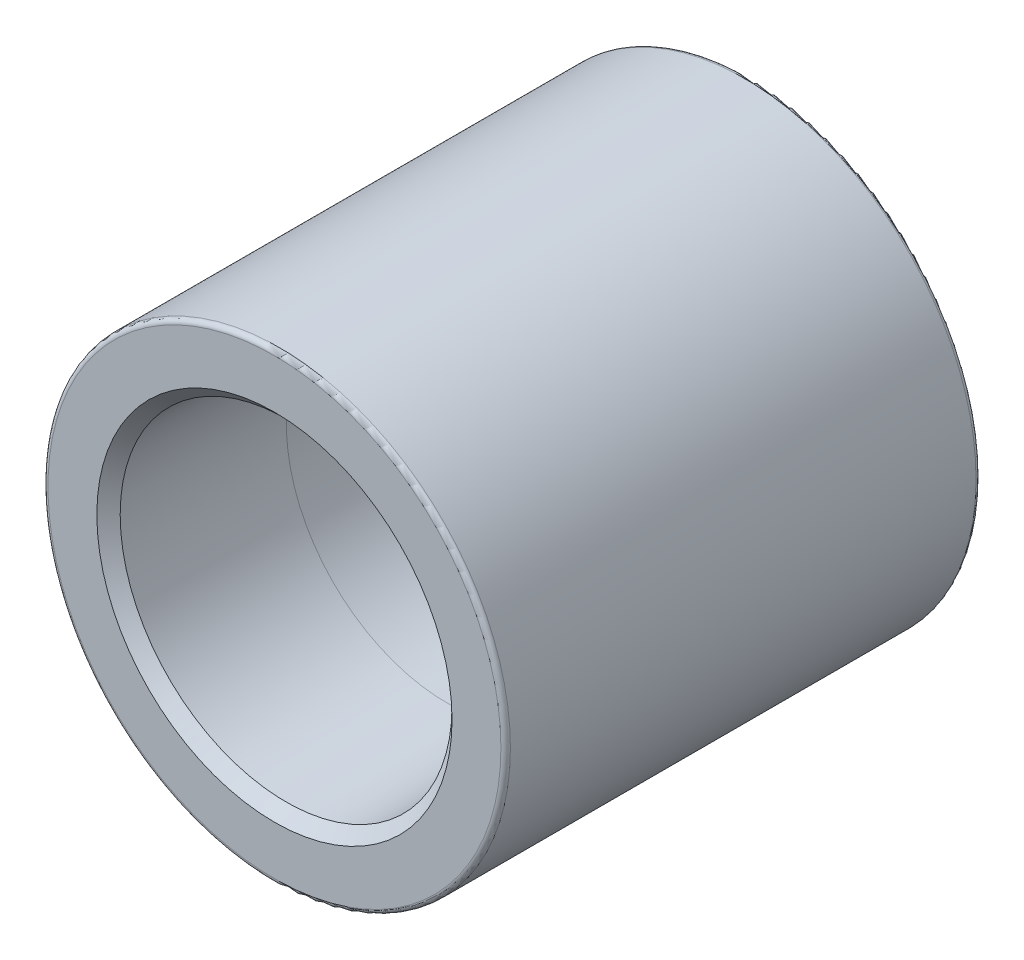
SolidWorks part; units mm, degrees
ref_plane "Front Plane" through (0, 0, 0) normal (0, 0, 1) x (1, 0, 0)
ref_plane "Top Plane" through (0, 0, 0) normal (0, 1, 0) x (1, 0, 0)
ref_plane "Right Plane" through (0, 0, 0) normal (1, 0, 0) x (0, 0, -1)
sketch "Sketch1" plane through (0, 0, 0) normal (0, 0, 1) x (1, 0, 0)
  circle A0 centre (0, 0) radius 18.542
  dimension "A" = 37.084
extrude "Extrude1" add sketch "Sketch1" along normal mid plane 38.1
sketch "Sketch2" plane through (0, 0, 19.05) normal (0, 0, 1) x (1, 0, 0)
  circle A0 centre (0, 0) radius 13.335
  dimension "pipe ID" = 26.67
extrude "Cut-Extrude1" cut sketch "Sketch2" against normal blind 13.8608 draft 1.783
sketch "Sketch3" plane through (0, 0, 5.1892) normal (0, 0, 1) x (1, 0, 0)
  circle A1 centre (0, 0) radius 12.9034
  circle A2 centre (0, 0) radius 12.9034 construction
curve "Helix/Spiral1" parameters "pitch"=1.8143
sketch "Sketch5" plane through (0, 0, 19.05) normal (0, 0, 1) x (1, 0, 0)
  line L0 (0, 14.2421) -> (0, 0) construction
  line L1 (0, 0) -> (-10.0707, 10.0707) construction
  circle A1 centre (0, 0) radius 14.2421
  circle A2 centre (0, 0) radius 13.335 construction
  dimension "D1" = 0.9071
  dimension "D2" = 45
sketch "Sketch4" plane through (0, 0, 0) normal (1, 0, 0) x (0, 0, -1)
  line L0 (-4.3955, 12.9034) -> (-5.0758, 11.725)
  line L1 (-5.0758, 11.725) -> (-5.3026, 11.725)
  line L2 (-5.3026, 11.725) -> (-6.0674, 13.0497)
  line L3 (-4.3955, 12.9034) -> (-5.983, 12.9034) construction
  line L4 (-4.3955, 12.9034) -> (-6.0674, 13.0497)
  line L5 (-5.1892, 11.725) -> (-5.1892, 12.9034) construction
  line L6 (-4.7356, 12.3142) -> (-5.6428, 12.3142) construction
  line L7 (-5.1892, 12.9034) -> (-5.1892, -12.9034) construction
  dimension "D1" = 5
  dimension "D2" = 60
  dimension "D3" = 0.2268
  dimension "D4" = 0.9071
sweep "Sweep1" [suppressed] add profiles "Sketch4" path "Helix/Spiral1"
sketch "Sketch6" plane through (0, 0, 19.05) normal (0, 0, 1) x (1, 0, 0)
  circle A1 centre (0, 0) radius 18.542
  circle A2 centre (0, 0) radius 18.542
  dimension "D1" = 0
extrude "Cut-Extrude2" [suppressed] cut sketch "Sketch6" along normal through all
extrude "Cut-Extrude3" cut sketch "Sketch5" against normal blind 3.175 draft 45
ref_axis "Axis1" through (0, 10.4775, 0) along (0, -1, 0)
pattern_circular "CirPattern1" count 2 over 360 about axis through (0, 10.4775, 0) along (0, -1, 0) of "Sweep1", "Cut-Extrude2", "Cut-Extrude3", "Cut-Extrude1"
sketch "Sketch7" plane through (0, 0, 0) normal (0, 0, 1) x (1, 0, 0)
  circle A3 centre (0, 0) radius 14.2421
  circle A4 centre (0, 0) radius 14.2421
  dimension "D2" = 0
extrude "Cut-Extrude4" [suppressed] cut sketch "Sketch7" along normal up to surface and the other way up to surface
fillet "Fillet1" radius 0.381 2 edges at (18.542, 0, -19.05) (18.542, 0, 19.05)
sketch "Sketch8" plane through (0, 0, 5.1892) normal (0, 0, 1) x (1, 0, 0)
  circle A1 centre (0, 0) radius 12.9034
  circle A2 centre (0, 0) radius 12.9034
  dimension "D1" = 0
extrude "Cut-Extrude5" cut sketch "Sketch8" against normal through all
equation "\"D3@Helix/Spiral1\" = \"E@Cut-Extrude1\"+ \"pitch@Helix/Spiral1\""
equation "\"D3@Sketch4\" = \"pitch@Helix/Spiral1\"*.125"
equation "\"D4@Sketch4\" = \"pitch@Helix/Spiral1\"*.5"
equation "\"D1@Sketch5\" = \"pitch@Helix/Spiral1\"*.5"
